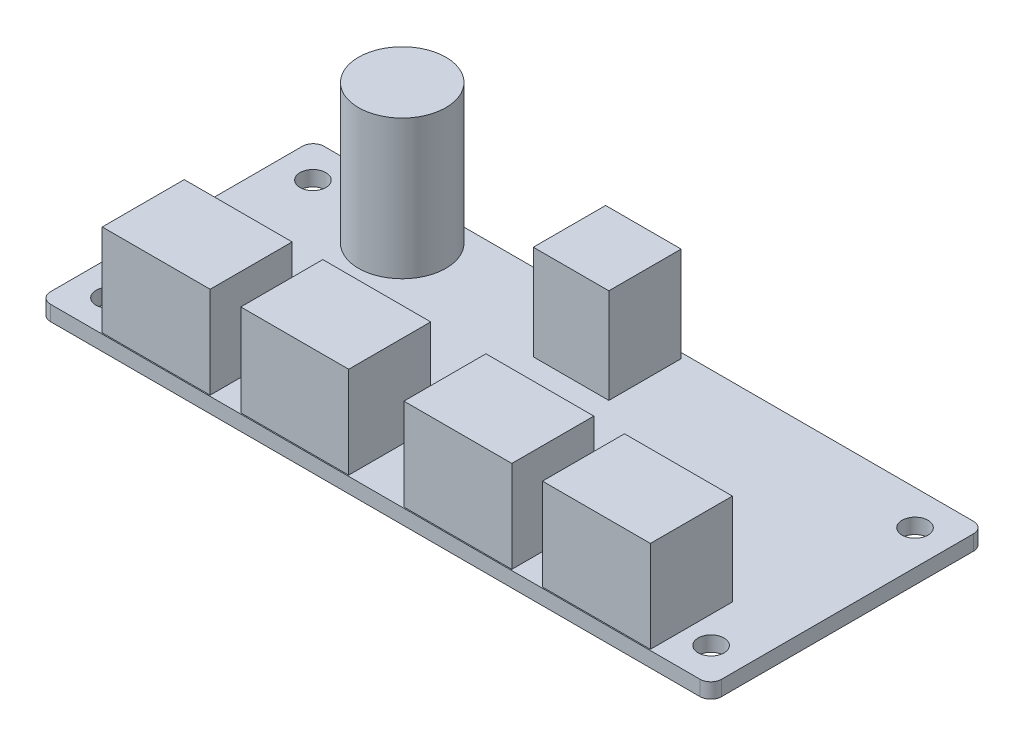
SolidWorks part; units mm, degrees
ref_plane "Front" through (0, 0, 0) normal (0, 0, 1) x (1, 0, 0)
ref_plane "Top" through (0, 0, 0) normal (0, 1, 0) x (1, 0, 0)
ref_plane "Right" through (0, 0, 0) normal (1, 0, 0) x (0, 0, -1)
sketch "Sketch1" plane through (0, 0, 0) normal (0, 1, 0) x (1, 0, 0)
  line L1 (-30.1, -12.675) -> (30.1, -12.675)
  line L2 (-31.1, -11.675) -> (-31.1, 11.675)
  line L3 (-30.1, 12.675) -> (30.1, 12.675)
  line L4 (31.1, -11.675) -> (31.1, 11.675)
  line L5 (-31.1, -12.675) -> (31.1, 12.675) construction
  line L6 (-31.1, 12.675) -> (31.1, -12.675) construction
  line L7 (-27.9, -9.45) -> (27.9, -9.45) construction
  line L8 (-27.9, -9.45) -> (-27.9, 9.45) construction
  line L9 (-27.9, 9.45) -> (27.9, 9.45) construction
  line L10 (27.9, -9.45) -> (27.9, 9.45) construction
  line L11 (-27.9, -9.45) -> (27.9, 9.45) construction
  line L12 (-27.9, 9.45) -> (27.9, -9.45) construction
  arc A0 (-30.1, -12.675) -> (-31.1, -11.675) centre (-30.1, -11.675) cw
  arc A1 (30.1, -12.675) -> (31.1, -11.675) centre (30.1, -11.675) ccw
  arc A2 (30.1, 12.675) -> (31.1, 11.675) centre (30.1, 11.675) cw
  arc A3 (-31.1, 11.675) -> (-30.1, 12.675) centre (-30.1, 11.675) cw
  circle A4 centre (-27.9, 9.45) radius 1.2
  circle A5 centre (-27.9, -9.45) radius 1.2
  circle A6 centre (27.9, -9.45) radius 1.2
  circle A7 centre (27.9, 9.45) radius 1.2
  point P0 (0, 0)
  point P18 (0, 0)
  dimension "D3" = 1
  dimension "D4" = 2.4
  dimension "D1" = 25.35
  dimension "D2" = 62.2
  dimension "D5" = 55.8
  dimension "D6" = 18.9
extrude "Boss-Extrude1" add sketch "Sketch1" along normal blind 1.4
sketch "Sketch2" plane through (0, 1.4, 0) normal (0, 1, 0) x (1, 0, 0)
  line L0 (30.1, 12.675) -> (-30.1, 12.675) construction
  line L1 (-3.5, 5.475) -> (3.5, 5.475)
  line L2 (-3.5, 5.475) -> (-3.5, 12.175)
  line L3 (-3.5, 12.175) -> (3.5, 12.175)
  line L4 (3.5, 5.475) -> (3.5, 12.175)
  line L5 (-3.5, 5.475) -> (3.5, 12.175) construction
  line L6 (-3.5, 12.175) -> (3.5, 5.475) construction
  point P0 (0, 8.825)
  point P7 (0, 0)
  dimension "D1" = 0.5
  dimension "D2" = 6.7
  dimension "D3" = 7
extrude "Boss-Extrude2" add sketch "Sketch2" along normal blind 8.8
sketch "Sketch3" plane through (0, 1.4, 0) normal (0, 1, 0) x (1, 0, 0)
  line L0 (-25.4, -8.775) -> (25.4, -8.775) construction
  line L1 (-25.4, -12.575) -> (-15.4, -12.575)
  line L2 (-25.4, -12.575) -> (-25.4, -4.975)
  line L3 (-25.4, -4.975) -> (-15.4, -4.975)
  line L4 (-15.4, -12.575) -> (-15.4, -4.975)
  line L5 (-25.4, -12.575) -> (-15.4, -4.975) construction
  line L6 (-25.4, -4.975) -> (-15.4, -12.575) construction
  line L7 (-12.56, -12.575) -> (-2.56, -12.575)
  line L8 (-12.56, -12.575) -> (-12.56, -4.975)
  line L9 (-12.56, -4.975) -> (-2.56, -4.975)
  line L10 (-2.56, -12.575) -> (-2.56, -4.975)
  line L11 (-12.56, -12.575) -> (-2.56, -4.975) construction
  line L12 (-12.56, -4.975) -> (-2.56, -12.575) construction
  line L13 (-30.1, -12.675) -> (30.1, -12.675) construction
  point P0 (-20.4, -8.775)
  point P5 (-7.56, -8.775)
  point P10 (22.5682, -8.633)
  point P13 (0, -8.775)
  point P14 (0, 0)
  point P16 (-24.8794, -8.701)
  point P17 (-9.3128, -8.1572)
  point P18 (-15.4, -3.7735)
  point P19 (-9.2102, -7.5735)
  point P20 (-15.4, -3.2682)
  point P23 (-2.3946, -4.975)
  dimension "D1" = 50.8
  dimension "D2" = 10
  dimension "D3" = 7.6
  dimension "D4" = 0.1
  dimension "D5" = 2.84
extrude "Boss-Extrude3" add sketch "Sketch3" along normal blind 8.5
mirror "Mirror1" about plane through (0, 0, 0) normal (1, 0, 0) of "Boss-Extrude3"
sketch "Sketch4" plane through (0, 1.4, 0) normal (0, 1, 0) x (1, 0, 0)
  line L0 (-31.1, 11.675) -> (-31.1, -11.675) construction
  line L1 (30.1, 12.675) -> (-30.1, 12.675) construction
  circle A0 centre (-18.7, 8.525) radius 4.05
  dimension "D2" = 8.1
  dimension "D1" = 12.4
  dimension "D3" = 4.15
extrude "Boss-Extrude4" add sketch "Sketch4" along normal blind 12.9
